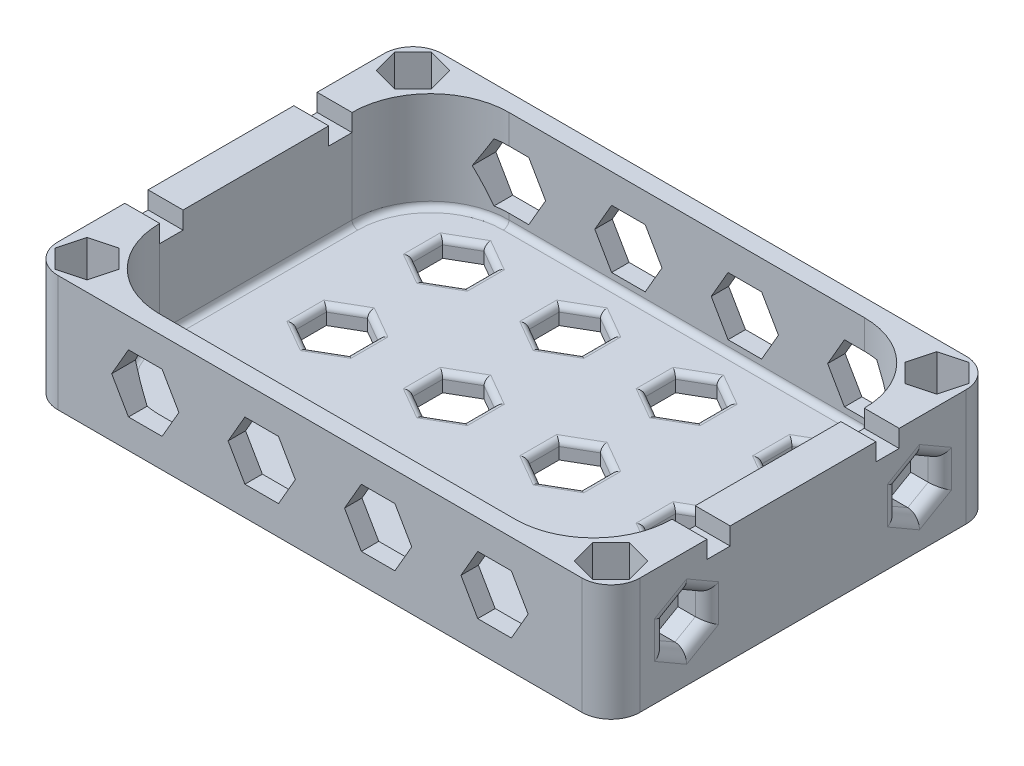
SolidWorks part; units mm, degrees
note: The reader was unsure of these and kept them because the rebuilt part matched: shared geometry of "Sketch3<7>".
ref_plane "Front Plane" through (0, 0, 0) normal (0, 0, 1) x (1, 0, 0)
ref_plane "Top Plane" through (0, 0, 0) normal (0, 1, 0) x (1, 0, 0)
ref_plane "Right Plane" through (0, 0, 0) normal (1, 0, 0) x (0, 0, -1)
sketch "Sketch3" plane through (0, 0, 0) normal (0, -1, 0) x (1, 0, 0)
  line L0 (-60, 20) -> (-80, 20)
  line L1 (-90, 23) -> (-100, 23)
  line L2 (-80, -5.1962) -> (-75.5, -2.5981)
  line L3 (-90, -23) -> (-100, -23)
  line L4 (-6, 23) -> (-6, -23)
  line L5 (-60, 0) -> (-40, 0)
  line L6 (-94, 23) -> (-94, -23)
  line L7 (-75.5, -2.5981) -> (-75.5, 2.5981)
  line L8 (-75.5, 2.5981) -> (-80, 5.1962)
  line L9 (-80, 5.1962) -> (-84.5, 2.5981)
  line L10 (-84.5, 2.5981) -> (-84.5, -2.5981)
  line L11 (-100, -23) -> (-100, -33)
  line L12 (-100, 23) -> (-100, 33)
  line L13 (-100, 33) -> (-10, 33)
  line L14 (-10, 33) -> (0, 33)
  line L15 (0, 33) -> (0, -23)
  line L16 (-90, 23) -> (-90, 33)
  line L17 (0, 33) -> (0, 23)
  line L18 (0, 23) -> (-10, 23)
  line L19 (-100, -33) -> (-10, -33)
  line L20 (-10, -33) -> (-10, -23)
  line L21 (-10, -33) -> (0, -33)
  line L22 (0, -33) -> (0, -23)
  line L23 (-10, 23) -> (-10, 33)
  line L24 (-90, -23) -> (-90, -33)
  line L49 (-10, -23) -> (0, -23)
  line L50 (-100, 33) -> (-90, 23)
  line L65 (0, 33) -> (-10, 23)
  line L67 (0, -33) -> (-10, -23)
  line L69 (-90, -23) -> (-100, -33)
  line L76 (-90, 30) -> (-10, 30)
  line L83 (-90, -30) -> (-10, -30)
  line L84 (-84.5, -2.5981) -> (-80, -5.1962)
  line L85 (-40, 0) -> (-20, 0)
  line L86 (-20, 0) -> (-20, 20)
  line L87 (-20, -20) -> (-20, 0)
  line L88 (-60, -20) -> (-40, -20)
  line L89 (-40, -20) -> (-20, -20)
  line L90 (-60, -20) -> (-60, 0)
  line L91 (-60, 20) -> (-40, 20)
  line L92 (-40, 20) -> (-20, 20)
  line L93 (-60, 0) -> (-60, 20)
  line L94 (-40, 20) -> (-40, 0)
  line L95 (-40, 0) -> (-40, -20)
  line L96 (0, 23) -> (0, -23)
  line L97 (0, 0) -> (-20, 0)
  line L98 (-80, -25.1962) -> (-75.5, -22.5981)
  line L99 (-55.5, 17.4019) -> (-55.5, 22.5981)
  line L100 (-55.5, 22.5981) -> (-60, 25.1962)
  line L101 (-60, 25.1962) -> (-64.5, 22.5981)
  line L102 (-64.5, 22.5981) -> (-64.5, 17.4019)
  line L103 (-64.5, 17.4019) -> (-60, 14.8038)
  line L104 (-60, 14.8038) -> (-55.5, 17.4019)
  line L105 (-35.5, 17.4019) -> (-35.5, 22.5981)
  line L106 (-35.5, 22.5981) -> (-40, 25.1962)
  line L107 (-40, 25.1962) -> (-44.5, 22.5981)
  line L108 (-44.5, 22.5981) -> (-44.5, 17.4019)
  line L109 (-44.5, 17.4019) -> (-40, 14.8038)
  line L110 (-40, 14.8038) -> (-35.5, 17.4019)
  line L111 (-24.5, 17.4019) -> (-20, 14.8038)
  line L112 (-20, 14.8038) -> (-15.5, 17.4019)
  line L113 (-15.5, 17.4019) -> (-15.5, 22.5981)
  line L114 (-15.5, 22.5981) -> (-20, 25.1962)
  line L115 (-20, 25.1962) -> (-24.5, 22.5981)
  line L116 (-24.5, 22.5981) -> (-24.5, 17.4019)
  line L117 (-24.5, 2.5981) -> (-24.5, -2.5981)
  line L118 (-24.5, -2.5981) -> (-20, -5.1962)
  line L119 (-20, -5.1962) -> (-15.5, -2.5981)
  line L120 (-15.5, -2.5981) -> (-15.5, 2.5981)
  line L121 (-15.5, 2.5981) -> (-20, 5.1962)
  line L122 (-20, 5.1962) -> (-24.5, 2.5981)
  line L123 (-40, 5.1962) -> (-44.5, 2.5981)
  line L124 (-44.5, 2.5981) -> (-44.5, -2.5981)
  line L125 (-44.5, -2.5981) -> (-40, -5.1962)
  line L126 (-40, -5.1962) -> (-35.5, -2.5981)
  line L127 (-35.5, -2.5981) -> (-35.5, 2.5981)
  line L128 (-35.5, 2.5981) -> (-40, 5.1962)
  line L129 (-60, 5.1962) -> (-64.5, 2.5981)
  line L130 (-64.5, 2.5981) -> (-64.5, -2.5981)
  line L131 (-64.5, -2.5981) -> (-60, -5.1962)
  line L132 (-60, -5.1962) -> (-55.5, -2.5981)
  line L133 (-55.5, -2.5981) -> (-55.5, 2.5981)
  line L134 (-55.5, 2.5981) -> (-60, 5.1962)
  line L135 (-64.5, -17.4019) -> (-64.5, -22.5981)
  line L136 (-64.5, -22.5981) -> (-60, -25.1962)
  line L137 (-60, -25.1962) -> (-55.5, -22.5981)
  line L138 (-55.5, -22.5981) -> (-55.5, -17.4019)
  line L139 (-55.5, -17.4019) -> (-60, -14.8038)
  line L140 (-60, -14.8038) -> (-64.5, -17.4019)
  line L141 (-44.5, -22.5981) -> (-40, -25.1962)
  line L142 (-40, -25.1962) -> (-35.5, -22.5981)
  line L143 (-35.5, -22.5981) -> (-35.5, -17.4019)
  line L144 (-35.5, -17.4019) -> (-40, -14.8038)
  line L145 (-40, -14.8038) -> (-44.5, -17.4019)
  line L146 (-44.5, -17.4019) -> (-44.5, -22.5981)
  line L147 (-20, -25.1962) -> (-15.5, -22.5981)
  line L148 (-15.5, -22.5981) -> (-15.5, -17.4019)
  line L149 (-15.5, -17.4019) -> (-20, -14.8038)
  line L150 (-20, -14.8038) -> (-24.5, -17.4019)
  line L151 (-24.5, -17.4019) -> (-24.5, -22.5981)
  line L152 (-24.5, -22.5981) -> (-20, -25.1962)
  line L153 (-8.1639, 31.1639) -> (-9.322, 26.8419)
  line L154 (-9.322, 26.8419) -> (-6.1581, 23.678)
  line L155 (-6.1581, 23.678) -> (-1.8361, 24.8361)
  line L156 (-1.8361, 24.8361) -> (-0.678, 29.1581)
  line L157 (-0.678, 29.1581) -> (-3.8419, 32.322)
  line L158 (-3.8419, 32.322) -> (-8.1639, 31.1639)
  line L165 (-99.322, -29.1581) -> (-96.1581, -32.322)
  line L166 (-96.1581, -32.322) -> (-91.8361, -31.1639)
  line L167 (-91.8361, -31.1639) -> (-90.678, -26.8419)
  line L168 (-90.678, -26.8419) -> (-93.8419, -23.678)
  line L169 (-93.8419, -23.678) -> (-98.1639, -24.8361)
  line L170 (-98.1639, -24.8361) -> (-99.322, -29.1581)
  line L171 (-1.8361, -24.8361) -> (-6.1581, -23.678)
  line L172 (-6.1581, -23.678) -> (-9.322, -26.8419)
  line L173 (-9.322, -26.8419) -> (-8.1639, -31.1639)
  line L174 (-8.1639, -31.1639) -> (-3.8419, -32.322)
  line L175 (-3.8419, -32.322) -> (-0.678, -29.1581)
  line L176 (-0.678, -29.1581) -> (-1.8361, -24.8361)
  line L183 (-99.322, 29.1581) -> (-98.1639, 24.8361)
  line L184 (-98.1639, 24.8361) -> (-93.8419, 23.678)
  line L185 (-93.8419, 23.678) -> (-90.678, 26.8419)
  line L186 (-90.678, 26.8419) -> (-91.8361, 31.1639)
  line L187 (-91.8361, 31.1639) -> (-96.1581, 32.322)
  line L188 (-96.1581, 32.322) -> (-99.322, 29.1581)
  line L189 (-75.5, -22.5981) -> (-75.5, -17.4019)
  line L190 (-100, -23) -> (-100, 23)
  line L191 (-75.5, -17.4019) -> (-80, -14.8038)
  line L192 (-80, -14.8038) -> (-84.5, -17.4019)
  line L193 (-84.5, -17.4019) -> (-84.5, -22.5981)
  line L194 (-84.5, -22.5981) -> (-80, -25.1962)
  line L195 (-80, 25.1962) -> (-84.5, 22.5981)
  line L196 (-84.5, 22.5981) -> (-84.5, 17.4019)
  line L197 (-84.5, 17.4019) -> (-80, 14.8038)
  line L198 (-80, 14.8038) -> (-75.5, 17.4019)
  line L199 (-75.5, 17.4019) -> (-75.5, 22.5981)
  line L200 (-75.5, 22.5981) -> (-80, 25.1962)
  line L201 (-80, 20) -> (-80, 0)
  line L202 (-80, 0) -> (-80, -20)
  line L203 (-80, -20) -> (-60, -20)
  line L204 (-60, 0) -> (-80, 0)
  arc A2 (-6, -16.5167) -> (-19.4833, -30) centre (-19.4833, -16.5167) cw
  circle A3 centre (-5, 28) radius 5
  circle A4 centre (-5, -28) radius 5
  circle A6 centre (-95, 28) radius 5
  circle A8 centre (-95, -28) radius 5
  arc A11 (-19.4833, 30) -> (-6, 16.5167) centre (-19.4833, 16.5167) cw
  circle A12 centre (-60, 20) radius 4.5
  circle A13 centre (-40, 20) radius 4.5
  arc A14 (-94, 16.5167) -> (-80.5167, 30) centre (-80.5167, 16.5167) cw
  arc A15 (-94, -16.5167) -> (-80.5167, -30) centre (-80.5167, -16.5167) ccw
  circle A16 centre (-95, 28) radius 3.875
  circle A17 centre (-5, 28) radius 3.875
  circle A18 centre (-5, -28) radius 3.875
  circle A19 centre (-95, -28) radius 3.875
  circle A20 centre (-20, 20) radius 4.5
  circle A21 centre (-20, -20) radius 4.5
  circle A22 centre (-40, -20) radius 4.5
  circle A23 centre (-60, -20) radius 4.5
  circle A24 centre (-60, 0) radius 4.5
  circle A25 centre (-40, 0) radius 4.5
  circle A26 centre (-20, 0) radius 4.5
  circle A27 centre (-60, 20) radius 4.5 construction
  circle A28 centre (-40, 20) radius 4.5 construction
  circle A29 centre (-20, 20) radius 4.5 construction
  circle A30 centre (-20, 0) radius 4.5 construction
  circle A31 centre (-40, 0) radius 4.5 construction
  circle A32 centre (-60, 0) radius 4.5 construction
  circle A33 centre (-60, -20) radius 4.5 construction
  circle A34 centre (-40, -20) radius 4.5 construction
  circle A35 centre (-20, -20) radius 4.5 construction
  circle A36 centre (-5, 28) radius 3.875 construction
  circle A37 centre (-95, 28) radius 3.875 construction
  circle A38 centre (-95, -28) radius 3.875 construction
  circle A39 centre (-5, -28) radius 3.875 construction
  circle A40 centre (-80, 0) radius 4.5 construction
  circle A41 centre (-80, -20) radius 4.5 construction
  circle A42 centre (-80, 20) radius 4.5 construction
  dimension "D5" = 3
  dimension "D3" = 10
  dimension "D8" = 9
  dimension "D4" = 7.75
  dimension "D9" = 20
  dimension "D12" = 100
  dimension "D1" = 6
  dimension "D2" = 3
  dimension "D6" = 60
  dimension "D7" = 6
  dimension "D10" = 20
  dimension "D11" = 20
extrude "Boss-Extrude7" add sketch "Sketch3" against normal blind 20 contours A4 L67 L175 L176 L171 L172 | A4 L67 L172 L173 L174 L175 | L22 A4 L49 | L49 A4 L67 A2 | A2 A4 L20 | L67 A4 A2 | L20 A4 L21 | A2 L20 L83 | L24 L83 L20 L19 | L97 L96 L49 L4 | A2 L4 L49 | L15 L97 L4 L18 | A11 L18 L4 | A11 L65 A3 L18 | A11 L23 A3 | A11 L76 L23 | A11 A3 L65 | A3 L65 L157 L158 L153 L154 | A3 L65 L154 L155 L156 L157 | L18 A3 L17 | L76 L16 L13 L23 | L14 A3 L23 | L24 A15 L83 | L19 A8 L24 | A8 L69 L165 L166 L167 L168 | A8 L69 L168 L169 L170 L165 | L3 A8 L11 | L69 A15 A8 | L3 A15 L69 A8 | A8 A15 L24 | L3 L190 L1 L6 | L6 A15 L3 | A14 L6 L1 | A14 L1 A6 L50 | A14 L50 A6 | A14 A6 L16 | A6 L50 L185 L186 L187 L188 | A6 L50 L188 L183 L184 L185 | L12 A6 L1 | L16 A6 L13 | A14 L16 L76
extrude "Boss-Extrude9" add sketch "Sketch3<7>" against normal blind 3
sketch "Sketch3<7>" plane through (0, 0, 0) normal (0, -1, 0) x (1, 0, 0) same geometry as "Sketch3"
sketch "Sketch5" plane through (-100, 0, 0) normal (-1, 0, 0) x (0, 0, 1)
  line L1 (-20, 5.4585) -> (-16.5, 7.4793)
  line L2 (-16.5, 7.4793) -> (-16.5, 11.5207)
  line L3 (-16.5, 11.5207) -> (-20, 13.5415)
  line L4 (-20, 13.5415) -> (-23.5, 11.5207)
  line L5 (-23.5, 11.5207) -> (-23.5, 7.4793)
  line L6 (-23.5, 7.4793) -> (-20, 5.4585)
  line L7 (23.5, 7.4793) -> (23.5, 11.5207)
  line L8 (23.5, 11.5207) -> (20, 13.5415)
  line L9 (20, 13.5415) -> (16.5, 11.5207)
  line L10 (16.5, 11.5207) -> (16.5, 7.4793)
  line L11 (16.5, 7.4793) -> (20, 5.4585)
  line L12 (20, 5.4585) -> (23.5, 7.4793)
  line L13 (-20, 9.5) -> (20, 9.5)
  line L18 (0, 0) -> (0, 9.5)
  line L20 (-28, 20) -> (28, 20) construction
  circle A0 centre (-20, 9.5) radius 3.5 construction
  circle A1 centre (20, 9.5) radius 3.5 construction
  circle A2 centre (-20, 9.5) radius 3.5
  circle A3 centre (20, 9.5) radius 3.5
  dimension "D3" = 7
  dimension "D1" = 40
  dimension "D2" = 10.5
  dimension "D4" = 10.5
extrude "Cut-Extrude1" cut sketch "Sketch5" against normal blind 5
sketch "Sketch6" plane through (0, 0, 0) normal (1, 0, 0) x (0, 0, -1)
  line L0 (-28, 20) -> (28, 20) construction
  line L1 (-20, 5.4585) -> (-16.5, 7.4793)
  line L2 (-16.5, 7.4793) -> (-16.5, 11.5207)
  line L3 (-16.5, 11.5207) -> (-20, 13.5415)
  line L4 (-20, 13.5415) -> (-23.5, 11.5207)
  line L5 (-23.5, 11.5207) -> (-23.5, 7.4793)
  line L6 (-23.5, 7.4793) -> (-20, 5.4585)
  line L7 (20, 5.4585) -> (23.5, 7.4793)
  line L8 (23.5, 7.4793) -> (23.5, 11.5207)
  line L9 (23.5, 11.5207) -> (20, 13.5415)
  line L10 (20, 13.5415) -> (16.5, 11.5207)
  line L11 (16.5, 11.5207) -> (16.5, 7.4793)
  line L12 (16.5, 7.4793) -> (20, 5.4585)
  line L15 (0, 0) -> (0, 9.5)
  line L16 (-20, 9.5) -> (20, 9.5)
  circle A0 centre (-20, 9.5) radius 3.5 construction
  circle A1 centre (20, 9.5) radius 3.5 construction
  circle A2 centre (-20, 9.5) radius 3.5
  circle A3 centre (20, 9.5) radius 3.5
  dimension "D1" = 7
  dimension "D2" = 40
  dimension "D3" = 10.5
extrude "Cut-Extrude2" cut sketch "Sketch6" against normal blind 5 contours L4 L5 L6 L1 L2 L3 | L10 L11 L12 L7 L8 L9
fillet "Fillet3" radius 2 24 edges at (0, 9.5, -16.5) (0, 6.4689, -18.25) (0, 6.4689, -21.75) (0, 9.5, -23.5) (0, 12.5311, -21.75) (0, 12.5311, -18.25) (0, 6.4689, 21.75) (0, 9.5, 23.5) (0, 12.5311, 21.75) (0, 12.5311, 18.25) (0, 9.5, 16.5) (0, 6.4689, 18.25) (-100, 12.5311, 18.25) (-100, 6.4689, 21.75) (-100, 9.5, 23.5) (-100, 12.5311, 21.75) (-100, 9.5, 16.5) (-100, 6.4689, 18.25) (-100, 6.4689, -18.25) (-100, 9.5, -16.5) (-100, 12.5311, -21.75) (-100, 12.5311, -18.25) (-100, 9.5, -23.5) (-100, 6.4689, -21.75)
fillet "Fillet4" radius 1 44 edges at (-50, 3, -30) (-90.0508, 3, -26.0508) (-94, 3, 0) (-44.5, 3, 0) (-35.5, 3, 0) (-55.5, 3, 20) (-64.5, 3, 20) (-75.5, 3, 0) (-82.25, 3, 3.8971) (-84.5, 3, 0) (-82.25, 3, -3.8971) (-55.5, 3, 0) (-64.5, 3, 0) (-35.5, 3, 20) (-44.5, 3, 20) (-44.5, 3, -20) (-35.5, 3, -20) (-24.5, 3, 0) (-17.75, 3, -3.8971) (-15.5, 3, 0) (-17.75, 3, 3.8971) (-90.0508, 3, 26.0508) (-50, 3, 30) (-9.9492, 3, 26.0508) (-6, 3, 0) (-9.9492, 3, -26.0508) (-17.75, 3, 16.1029) (-15.5, 3, 20) (-17.75, 3, 23.8971) (-24.5, 3, 20) (-75.5, 3, 20) (-82.25, 3, 23.8971) (-84.5, 3, 20) (-82.25, 3, 16.1029) (-82.25, 3, -16.1029) (-84.5, 3, -20) (-82.25, 3, -23.8971) (-75.5, 3, -20) (-24.5, 3, -20) (-17.75, 3, -23.8971) (-15.5, 3, -20) (-17.75, 3, -16.1029) (-64.5, 3, -20) (-55.5, 3, -20)
sketch "Sketch7" plane through (0, 20, 0) normal (0, 1, 0) x (1, 0, 0)
  line L0 (-100, 28) -> (-100, -28) construction
  line L1 (-100, 16.5167) -> (-94, 16.5167)
  line L2 (-100, 16.5167) -> (-100, 12.5167)
  line L3 (-100, 12.5167) -> (-94, 12.5167)
  line L4 (-94, 16.5167) -> (-94, 12.5167)
  line L5 (-94, -16.5167) -> (-94, 16.5167) construction
  line L6 (0, -28) -> (0, 28) construction
  line L7 (-100, -12.5167) -> (-94, -12.5167)
  line L8 (-100, -12.5167) -> (-100, -16.5167)
  line L9 (-100, -16.5167) -> (-94, -16.5167)
  line L10 (-94, -12.5167) -> (-94, -16.5167)
  line L11 (0, 16.5167) -> (-6, 16.5167)
  line L12 (0, 16.5167) -> (0, 12.5167)
  line L13 (0, 12.5167) -> (-6, 12.5167)
  line L14 (-6, 16.5167) -> (-6, 12.5167)
  line L15 (-6, -16.5167) -> (-6, 16.5167) construction
  line L16 (0, -16.5167) -> (-6, -16.5167)
  line L17 (0, -16.5167) -> (0, -12.5167)
  line L18 (0, -12.5167) -> (-6, -12.5167)
  line L19 (-6, -16.5167) -> (-6, -12.5167)
  line L20 (-6, 16.5167) -> (-6, -16.5167) construction
  line L21 (-94, -16.5167) -> (-94, 16.5167) construction
  dimension "D1" = 4
extrude "Cut-Extrude3" cut sketch "Sketch7" against normal blind 3
sketch "Sketch8" plane through (0, 0, 33) normal (0, 0, 1) x (1, 0, 0)
  line L0 (-100, 20) -> (0, 20)
  line L1 (-95, 0) -> (-5, 0) construction
  line L2 (-85.7735, 10) -> (-82.8868, 5)
  line L3 (-82.8868, 5) -> (-77.1132, 5)
  line L4 (-77.1132, 5) -> (-74.2265, 10)
  line L5 (-74.2265, 10) -> (-77.1132, 15)
  line L6 (-77.1132, 15) -> (-82.8868, 15)
  line L7 (-82.8868, 15) -> (-85.7735, 10)
  line L8 (-65.7735, 10) -> (-62.8868, 5)
  line L9 (-62.8868, 5) -> (-57.1132, 5)
  line L10 (-57.1132, 5) -> (-54.2265, 10)
  line L11 (-54.2265, 10) -> (-57.1132, 15)
  line L12 (-57.1132, 15) -> (-62.8868, 15)
  line L13 (-62.8868, 15) -> (-65.7735, 10)
  line L14 (-45.7735, 10) -> (-42.8868, 5)
  line L15 (-42.8868, 5) -> (-37.1132, 5)
  line L16 (-37.1132, 5) -> (-34.2265, 10)
  line L17 (-34.2265, 10) -> (-37.1132, 15)
  line L18 (-37.1132, 15) -> (-42.8868, 15)
  line L19 (-42.8868, 15) -> (-45.7735, 10)
  line L20 (-25.7735, 10) -> (-22.8868, 5)
  line L21 (-22.8868, 5) -> (-17.1132, 5)
  line L22 (-17.1132, 5) -> (-14.2265, 10)
  line L23 (-14.2265, 10) -> (-17.1132, 15)
  line L24 (-17.1132, 15) -> (-22.8868, 15)
  line L25 (-22.8868, 15) -> (-25.7735, 10)
  line L26 (-80, 10) -> (-60, 10)
  line L27 (-60, 10) -> (-40, 10)
  line L28 (-40, 10) -> (-20, 10)
  circle A0 centre (-80, 10) radius 5 construction
  circle A2 centre (-80, 10) radius 5
  circle A3 centre (-60, 10) radius 5
  circle A4 centre (-40, 10) radius 5
  circle A5 centre (-20, 10) radius 5
  dimension "D3" = 10
  dimension "D1" = 20
  dimension "D2" = 10
  dimension "D5" = 20
  dimension "D4" = 4
extrude "Cut-Extrude4" cut sketch "Sketch8" along normal through all both and the other way through all contours L4 L5 L6 L7 L2 L3 | L8 L9 L10 L11 L12 L13 | L14 L15 L16 L17 L18 L19 | L20 L21 L22 L23 L24 L25
